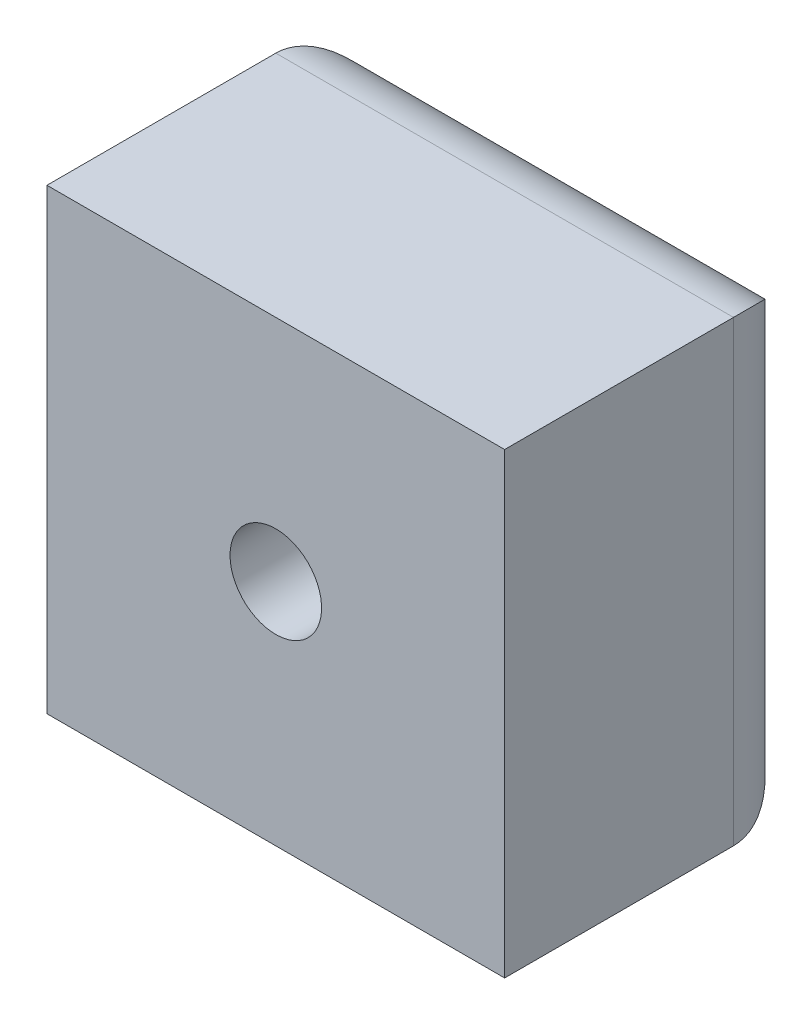
SolidWorks part; units mm, degrees
ref_plane "Front Plane" through (0, 0, 0) normal (0, 0, 1) x (1, 0, 0)
ref_plane "Top Plane" through (0, 0, 0) normal (0, 1, 0) x (1, 0, 0)
ref_plane "Right Plane" through (0, 0, 0) normal (1, 0, 0) x (0, 0, -1)
sketch "Sketch1" plane through (0, 0, 0) normal (0, 0, 1) x (1, 0, 0)
  line L1 (0, 0) -> (15, 0)
  line L2 (0, 0) -> (0, 15)
  line L3 (0, 15) -> (15, 15)
  line L4 (15, 0) -> (15, 15)
  dimension "D1" = 15
  dimension "D2" = 15
extrude "Boss-Extrude1" add sketch "Sketch1" along normal blind 10
fillet "Fillet2" radius 2.5 4 edges at (7.5, 0, 0) (15, 7.5, 0) (7.5, 15, 0) (0, 7.5, 0)
hole_wizard "M3x0.5 Tapped Hole1" positions "Sketch3" profile "Sketch4" tap size "M3x0.5" standard "ANSI Metric" end condition through all
sketch "Sketch3" plane through (0, 0, 0) normal (0, 0, -1) x (-1, 0, 0)
  line L0 (-7.5, 2.5) -> (-7.5, 12.5) construction
  line L1 (-12.5, 2.5) -> (-2.5, 2.5) construction
  line L2 (-2.5, 12.5) -> (-12.5, 12.5) construction
  line L5 (-12.5, 7.5) -> (-2.5, 7.5) construction
  line L6 (-12.5, 12.5) -> (-12.5, 2.5) construction
  line L7 (-2.5, 2.5) -> (-2.5, 12.5) construction
  point P20 (-7.5, 7.5)
sketch "Sketch4" plane through (7.5, 7.5, 0) normal (1, 0, 0) x (0, 1, 0)
  line L0 (0, 0) -> (0, 10)
  line L1 (0, 10) -> (1.5, 10)
  line L2 (1.5, 10) -> (1.5, 0)
  line L5 (1.5, 0) -> (0, 0)
  line L11 (0, -6.35) -> (0, 107.95) construction
  dimension "Thread Major Dia." = 3
  dimension "Thru Tap Drill Depth" = 10
sketch "Sketch5" plane through (0, 0, 0) normal (0, 0, -1) x (-1, 0, 0)
  line L0 (-12.5, 7.5) -> (-2.5, 7.5) construction
  line L1 (-12.5, 12.5) -> (-12.5, 2.5) construction
  line L2 (-2.5, 2.5) -> (-2.5, 12.5) construction
  line L3 (-7.5, 2.5) -> (-7.5, 12.5) construction
  line L4 (-12.5, 2.5) -> (-2.5, 2.5) construction
  line L5 (-2.5, 12.5) -> (-12.5, 12.5) construction
  circle A0 centre (-7.5, 7.5) radius 3
  dimension "D1" = 6
extrude "Cut-Extrude1" cut sketch "Sketch5" against normal blind 6
